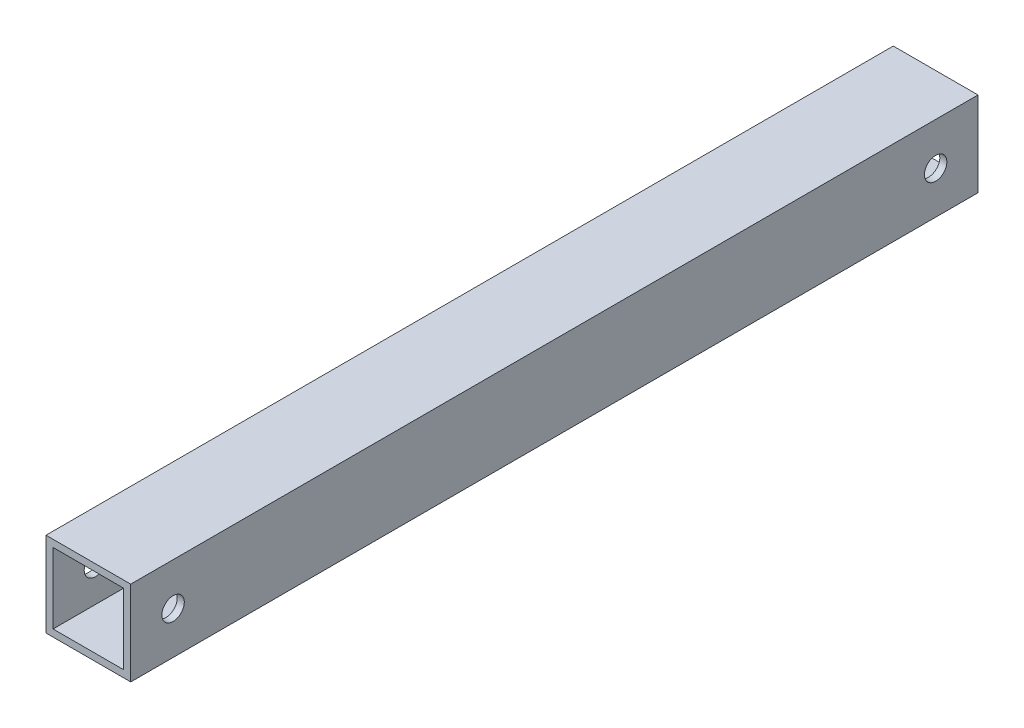
SolidWorks part; units mm, degrees
material "Plain Carbon Steel"
ref_plane "Front Plane" through (0, 0, 0) normal (0, 0, 1) x (1, 0, 0)
ref_plane "Top Plane" through (0, 0, 0) normal (0, 1, 0) x (1, 0, 0)
ref_plane "Right Plane" through (0, 0, 0) normal (1, 0, 0) x (0, 0, -1)
sketch "Sketch2" plane through (0, 0, 0) normal (0, 0, 1) x (1, 0, 0)
  line L0 (0, 19.05) -> (3.175, 19.05) construction
  line L1 (0, 0) -> (38.1, 0)
  line L2 (0, 0) -> (0, 38.1)
  line L3 (0, 38.1) -> (38.1, 38.1)
  line L4 (38.1, 0) -> (38.1, 38.1)
  line L5 (3.175, 3.175) -> (34.925, 3.175)
  line L6 (3.175, 3.175) -> (3.175, 34.925)
  line L7 (3.175, 34.925) -> (34.925, 34.925)
  line L8 (34.925, 3.175) -> (34.925, 34.925)
  line L9 (19.05, 34.925) -> (19.05, 38.1) construction
  line L10 (34.925, 19.05) -> (38.1, 19.05) construction
  line L11 (19.05, 0) -> (19.05, 3.175) construction
  dimension "D1" = 38.1
  dimension "D2" = 3.175
  dimension "D3" = 38.1
extrude "Boss-Extrude1" add sketch "Sketch2" along normal blind 381
hole_wizard "X (0.397) Diameter Hole1" positions "Sketch4" profile "Sketch3" hole size "X" standard "ANSI Inch" end condition through all
sketch "Sketch4" plane through (0, 0, 0) normal (-1, 0, 0) x (0, 0, 1)
  line L0 (0, 19.05) -> (19.05, 19.05) construction
  line L1 (0, 38.1) -> (0, 0) construction
  line L2 (19.05, 19.05) -> (361.95, 19.05) construction
  line L3 (361.95, 19.05) -> (381, 19.05) construction
  line L4 (381, 38.1) -> (381, 0) construction
  point P0 (19.05, 19.05)
  point P2 (361.95, 19.05)
  dimension "D1" = 19.05
sketch "Sketch3" plane through (0, 19.05, 19.05) normal (0, 1, 0) x (0, 0, 1)
  line L0 (0, 0) -> (0, 38.1)
  line L1 (0, 38.1) -> (5.0419, 38.1)
  line L2 (5.0419, 38.1) -> (5.0419, 0)
  line L5 (5.0419, 0) -> (0, 0)
  line L11 (0, -6.35) -> (0, 107.95) construction
  dimension "Thru Hole Dia." = 10.0838
  dimension "Thru Hole Depth" = 38.1
